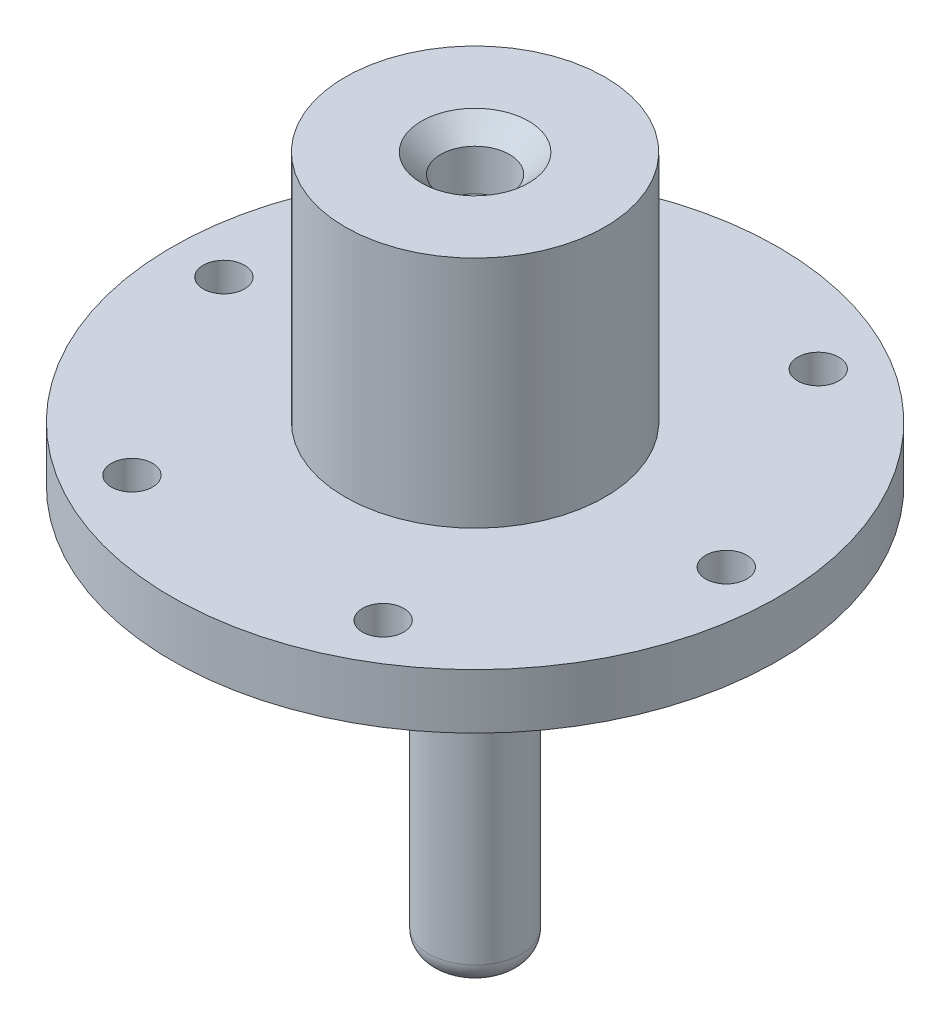
SolidWorks part; units mm, degrees
ref_plane "Front Plane" through (0, 0, 0) normal (0, 0, 1) x (1, 0, 0)
ref_plane "Top Plane" through (0, 0, 0) normal (0, 1, 0) x (1, 0, 0)
ref_plane "Right Plane" through (0, 0, 0) normal (1, 0, 0) x (0, 0, -1)
sketch "Sketch1" plane through (0, 0, 0) normal (0, 0, 1) x (1, 0, 0)
  line L0 (0, 0) -> (-15, 0)
  line L1 (-15, 0) -> (-15, -27)
  line L2 (-15, -27) -> (-35, -27)
  line L3 (-35, -27) -> (-35, -33.35)
  line L4 (-35, -33.35) -> (-16, -33.35)
  line L5 (-10, -35.85) -> (-10, -45.35)
  line L6 (-10, -45.35) -> (-5.3467, -50.0033)
  line L7 (-5.3467, -50.0033) -> (-5.3467, -77.5033)
  line L8 (-2.8467, -80.0033) -> (0, -80.0033)
  line L9 (0, -80.0033) -> (0, 0)
  line L11 (-10, -35.85) -> (-16, -35.85)
  line L12 (-16, -35.85) -> (-16, -33.35)
  arc A0 (-5.3467, -77.5033) -> (-2.8467, -80.0033) centre (-2.8467, -77.5033) ccw
  point P7 (-10, -33.35)
  point P15 (-5.3467, -80.0033)
  dimension "D9" = 2.5
  dimension "D1" = 5.3467
  dimension "D2" = 10
  dimension "D3" = 30
  dimension "D4" = 45
  dimension "D5" = 6.35
  dimension "D6" = 12
  dimension "D7" = 15
  dimension "D8" = 25
  dimension "D11" = 2.5
  dimension "D10" = 27
  dimension "D12" = 16
revolve "Revolve1" add sketch "Sketch1" angle 360 about L9
hole_wizard "1/16 NPT Tapped Hole1" positions "Sketch2" profile "Sketch4" size "1/16" standard "ANSI Inch"
sketch "Sketch2" plane through (0, 0, 0) normal (0, 1, 0) x (1, 0, 0)
  point P0 (0, 0)
sketch "Sketch4" plane through (0, 0, 0) normal (1, 0, 0) x (0, 0, 1)
  line L0 (0, 0) -> (0, 78.8467)
  line L1 (3.0734, 77) -> (0, 78.8467)
  line L2 (-3.0734, 77) -> (0, 78.8467) construction
  line L3 (3.0734, 77) -> (3.0734, 6.89)
  line L4 (3.0734, 6.89) -> (3.8291, 6.89)
  line L5 (3.8291, 6.89) -> (3.9689, 2.2224)
  line L6 (3.9689, 2.2224) -> (6.1913, 0)
  line L7 (6.1913, 0) -> (0, 0)
  line L8 (0, -6.35) -> (0, 107.95) construction
  line L9 (-3.9689, 2.2224) -> (-6.1913, 0) construction
  line L11 (-3.0734, 6.89) -> (-3.8291, 6.89) construction
  line L12 (-3.8291, 6.89) -> (-3.9689, 2.2224) construction
  dimension "Tap Drill Dia." = 6.1468
  dimension "Tap Drill Depth" = 77
  dimension "Thread Dia." = 7.9378
  dimension "Thread Angle" = 3.43
  dimension "Thread Depth" = 6.89
  dimension "C'Sink Dia." = 12.3825
  dimension "C'Sink Angle" = 90
  dimension "Drill Angle" = 118
sketch "Sketch5" plane through (0, -33.35, 0) normal (0, -1, 0) x (-1, 0, 0)
  circle A0 centre (0, 0) radius 21
  circle A1 centre (0, 0) radius 24
  dimension "D1" = 42
  dimension "D2" = 48
extrude "Cut-Extrude1" cut sketch "Sketch5" against normal blind 3
hole_wizard "3/16 (0.1875) Diameter Hole1" positions "Sketch6" profile "Sketch8" hole size "3/16" standard "ANSI Inch" end condition through all
sketch "Sketch6" plane through (0, -27, 0) normal (0, 1, 0) x (1, 0, 0)
  point P0 (29, 0)
  dimension "D1" = 29
sketch "Sketch8" plane through (29, -27, 0) normal (1, 0, 0) x (0, 0, 1)
  line L0 (0, 0) -> (0, 53.0033)
  line L1 (0, 53.0033) -> (2.3812, 53.0033)
  line L2 (2.3812, 53.0033) -> (2.3812, 0)
  line L5 (2.3812, 0) -> (0, 0)
  line L11 (0, -6.35) -> (0, 107.95) construction
  dimension "Thru Hole Dia." = 4.7625
  dimension "Thru Hole Depth" = 53.0033
pattern_circular "CirPattern1" count 6 over 360 about axis through (0, -80.0033, 0) along (0, -1, 0) of "3/16 (0.1875) Diameter Hole1" reverse direction yes
